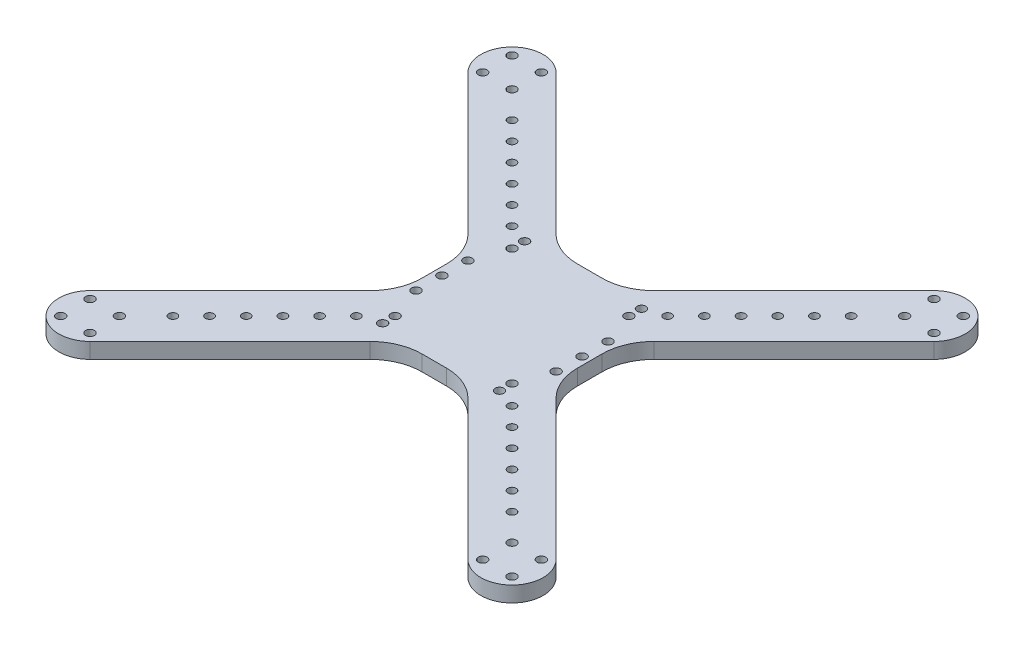
SolidWorks part; units mm, degrees
ref_plane "Front Plane" through (0, 0, 0) normal (0, 0, 1) x (1, 0, 0)
ref_plane "Top Plane" through (0, 0, 0) normal (0, 1, 0) x (1, 0, 0)
ref_plane "Right Plane" through (0, 0, 0) normal (1, 0, 0) x (0, 0, -1)
sketch "Sketch1" plane through (0, 0, 0) normal (0, 1, 0) x (1, 0, 0)
  line L0 (-81.3173, 81.3173) -> (81.3173, -81.3173) construction
  line L1 (-98.425, -98.425) -> (98.425, -98.425) construction
  line L2 (-98.425, -98.425) -> (-98.425, 98.425) construction
  line L3 (-98.425, 98.425) -> (98.425, 98.425) construction
  line L4 (98.425, -98.425) -> (98.425, 98.425) construction
  line L5 (-98.425, -98.425) -> (98.425, 98.425) construction
  line L6 (-98.425, 98.425) -> (98.425, -98.425) construction
  line L7 (-72.832, 89.8026) -> (-13.0294, 30)
  line L8 (-89.8026, 72.832) -> (-30, 13.0294)
  line L9 (0, 98.425) -> (0, -98.425) construction
  line L10 (81.3173, 81.3173) -> (-81.3173, -81.3173) construction
  line L11 (72.832, 89.8026) -> (13.0294, 30)
  line L12 (89.8026, 72.832) -> (30, 13.0294)
  line L13 (-30, -13.0294) -> (-89.8026, -72.832)
  line L14 (-13.0294, -30) -> (13.0294, -30)
  line L15 (-30, -13.0294) -> (-30, 13.0294)
  line L16 (-13.0294, 30) -> (13.0294, 30)
  line L17 (30, -13.0294) -> (30, 13.0294)
  line L18 (-30, -30) -> (30, 30) construction
  line L19 (-30, 30) -> (30, -30) construction
  line L20 (-13.0294, -30) -> (-72.832, -89.8026)
  line L21 (30, -13.0294) -> (89.8026, -72.832)
  line L22 (13.0294, -30) -> (72.832, -89.8026)
  arc A0 (-72.832, 89.8026) -> (-89.8026, 72.832) centre (-81.3173, 81.3173) ccw
  arc A1 (72.832, -89.8026) -> (89.8026, -72.832) centre (81.3173, -81.3173) ccw
  circle A2 centre (-81.3173, 81.3173) radius 8 construction
  circle A3 centre (81.3173, -81.3173) radius 8 construction
  circle A4 centre (-81.3173, -81.3173) radius 8 construction
  circle A5 centre (81.3173, 81.3173) radius 8 construction
  arc A6 (72.832, 89.8026) -> (89.8026, 72.832) centre (81.3173, 81.3173) cw
  arc A7 (-72.832, -89.8026) -> (-89.8026, -72.832) centre (-81.3173, -81.3173) cw
  point P0 (0, 0)
  point P8 (0, 0)
  point P23 (0, 0)
  point P29 (0, 0)
  point P42 (30, 0)
  dimension "D2" = 12
  dimension "D4" = 16
  dimension "D6" = 12
  dimension "D9" = 12
  dimension "D10" = 12
  dimension "D1" = 196.85
  dimension "D3" = 115
  dimension "D5" = 115
  dimension "D8" = 26.0589
  dimension "D11" = 30
  dimension "D12" = 30
extrude "Boss-Extrude1" add sketch "Sketch1" along normal blind 6
fillet "Fillet1" radius 20 8 edges at (-30, 3, -13.0294) (-30, 3, 13.0294) (-13.0294, 3, -30) (13.0294, 3, -30) (30, 3, 13.0294) (30, 3, -13.0294) (13.0294, 3, 30) (-13.0294, 3, 30)
ref_axis "Axis1" through (0, 6.3, 0) along (0, -1, 0)
ref_plane "Plane1" through (0, 0, 0) normal (-0.7071, 0, 0.7071) x (0, -1, 0)
sketch "Sketch2" plane through (0, 6, 0) normal (0, 1, 0) x (1, 0, 0)
  line L0 (0, 0) -> (-25, 0)
  line L1 (-25, 0) -> (-25, -25)
  line L2 (-25, -25) -> (0, -25)
  line L3 (0, -25) -> (0, 0)
  circle A1 centre (-22.525, -22.525) radius 1.7
  dimension "D4" = 3.4
  dimension "D1" = 25
  dimension "D2" = 22.525
  dimension "D3" = 22.525
extrude "Cut-Extrude1" cut sketch "Sketch2" against normal through all contours A1 region at (-22.525, 6, 22.525)
pattern_circular "CirPattern1" count 4 over 360 about axis through (0, 6.3, 0) along (0, -1, 0) of "Cut-Extrude1"
sketch "Sketch3" plane through (0, 6, 0) normal (0, 1, 0) x (1, 0, 0)
  line L0 (0, 0) -> (-89.8026, -89.8026) construction
  circle A0 centre (-30, -30) radius 1.6
  arc A1 (-89.8026, -72.832) -> (-72.832, -89.8026) centre (-81.3173, -81.3173) ccw construction
  dimension "D1" = 3.2
  dimension "D2" = 30
extrude "Cut-Extrude2" cut sketch "Sketch3" against normal through all
pattern_linear "LPattern1" count 6 spacing 10 along (-0.7071, 0, 0.7071) of "Cut-Extrude2"
pattern_circular "CirPattern2" count 4 over 360 about axis through (0, 6.3, 0) along (0, -1, 0) of "LPattern1"
sketch "Sketch4" plane through (0, 6, 0) normal (0, 1, 0) x (1, 0, 0)
  line L0 (-89.8026, -72.832) -> (-72.832, -89.8026) construction
  line L1 (-75.6604, -75.6604) -> (-86.9741, -86.9741) construction
  circle A0 centre (-81.3173, -81.3173) radius 8
  circle A1 centre (-86.9741, -86.9741) radius 1.7
  circle A2 centre (-86.9741, -75.6604) radius 1.7
  circle A3 centre (-75.6604, -75.6604) radius 1.7
  circle A4 centre (-75.6604, -86.9741) radius 1.7
  point P15 (0, 0)
  point P16 (0, 0)
  dimension "D1" = 16
  dimension "D2" = 3.4
extrude "Cut-Extrude3" cut sketch "Sketch4" against normal through all contours A0 A2 | A0 A2 | A0 A3 | A0 A3 | A0 A4 | A0 A4 | A0 A1 | A0 A1 region at (-76.1929, 6, 76.1929) region at (-75.1739, 6, 75.1739) region at (-75.1739, 6, 87.4606) region at (-76.1929, 6, 86.4416) region at (-86.4416, 6, 76.1929) region at (-87.4606, 6, 75.1739) region at (-87.4606, 6, 87.4606) region at (-86.4416, 6, 86.4416)
pattern_circular "CirPattern3" count 4 over 360 about axis through (0, 6.3, 0) along (0, -1, 0) of "Cut-Extrude3"
sketch "Sketch5" plane through (0, 6, 0) normal (0, 1, 0) x (1, 0, 0)
  line L0 (-22.525, -22.525) -> (-22.525, 27.375) construction
  line L1 (0, 0) -> (-22.525, 0) construction
  line L2 (-22.525, 0) -> (-22.525, -27.35) construction
  circle A0 centre (-22.525, 27.375) radius 1.7
  circle A1 centre (-22.525, -27.35) radius 1.7
  dimension "D2" = 3.4
  dimension "D5" = 3.4
  dimension "D1" = 49.9
  dimension "D3" = 27.375
  dimension "D4" = 27.35
extrude "Cut-Extrude4" cut sketch "Sketch5" against normal through all contours A0 | A1 region at (-22.525, 6, -27.375) region at (-22.525, 6, 27.35)
mirror "Mirror1" about plane through (0, 0, 0) normal (1, 0, 0) of "Cut-Extrude4"
sketch "Sketch6" plane through (0, 6, 0) normal (0, 1, 0) x (1, 0, 0)
  line L0 (-2.5668, 2.5668) -> (2.5668, -2.5668) construction
  line L1 (-89.8026, 72.832) -> (-72.832, 89.8026) construction
  circle A0 centre (-81.3173, 81.3173) radius 63.5
  point P6 (0, 0)
sketch "Sketch7" plane through (0, 6, 0) normal (0, 1, 0) x (1, 0, 0)
  line L0 (-30, 4.7452) -> (-30, -4.7452) construction
  line L1 (-27, 0) -> (0, 0) construction
  circle A0 centre (-27, 0) radius 1.7
  dimension "D1" = 3.4
  dimension "D2" = 3
extrude "Cut-Extrude5" cut sketch "Sketch7" against normal through all
pattern_linear "LPattern2" count 2 spacing 10 along (0, 0, 1) count 2 spacing 10 along (0, 0, -1) of "Cut-Extrude5"
mirror "Mirror2" about plane through (0, 0, 0) normal (1, 0, 0) of "LPattern2"
